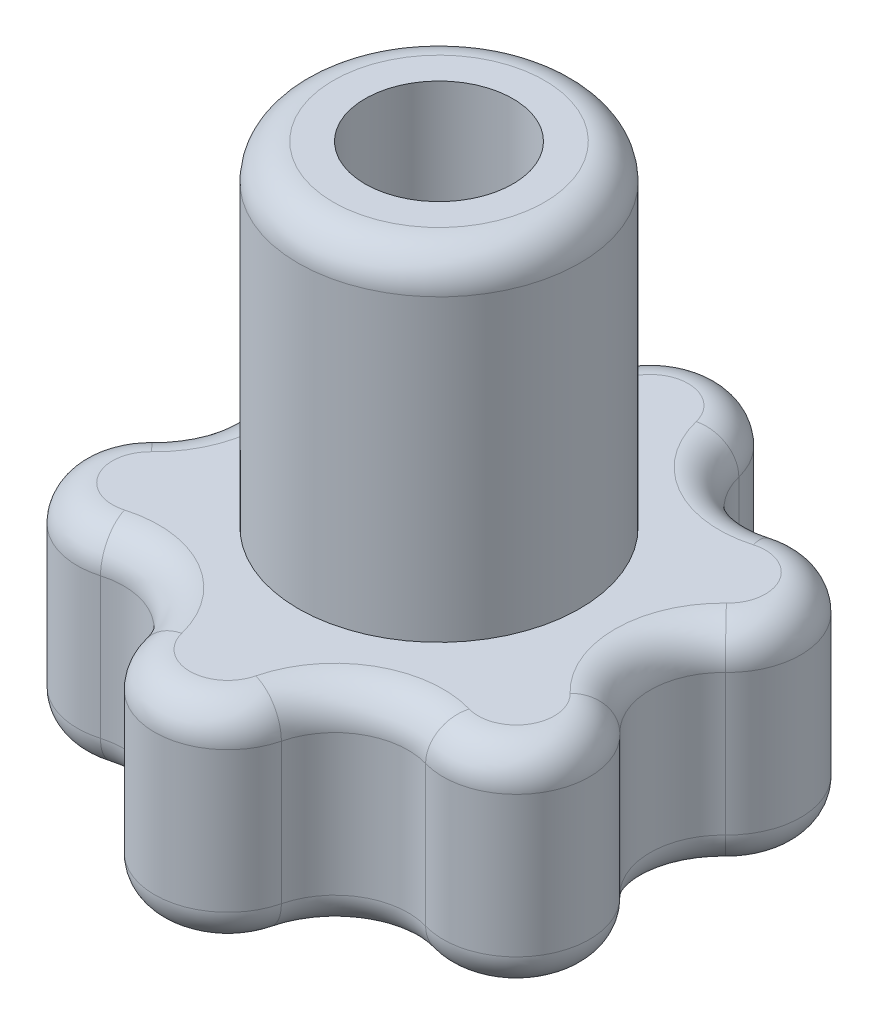
SolidWorks part; units mm, degrees
ref_plane "Спереди" through (0, 0, 0) normal (0, 0, 1) x (1, 0, 0)
ref_plane "Сверху" through (0, 0, 0) normal (0, 1, 0) x (1, 0, 0)
ref_plane "Справа" through (0, 0, 0) normal (1, 0, 0) x (0, 0, -1)
sketch "Эскиз1" plane through (0, 0, 0) normal (0, 1, 0) x (1, 0, 0)
  line L1 (0, 4.2147) -> (-3.65, 2.1073)
  line L2 (-3.65, 2.1073) -> (-3.65, -2.1073)
  line L3 (-3.65, -2.1073) -> (0, -4.2147)
  line L4 (0, -4.2147) -> (3.65, -2.1073)
  line L5 (3.65, -2.1073) -> (3.65, 2.1073)
  line L6 (3.65, 2.1073) -> (0, 4.2147)
  circle A0 centre (0, 0) radius 6 construction
  arc A1 (2.0203, 6.4992) -> (-2.0203, 6.4992) centre (0, 6) ccw
  arc A2 (2.0203, 6.4992) -> (4.6183, 4.9992) centre (4.0405, 6.9984) ccw
  arc A3 (-2.0203, -6.4992) -> (2.0203, -6.4992) centre (0, -6) ccw
  arc A4 (4.6183, -4.9992) -> (2.0203, -6.4992) centre (4.0405, -6.9984) ccw
  arc A5 (6.6386, 1.5) -> (4.6183, 4.9992) centre (5.1962, 3) ccw
  arc A6 (6.6386, 1.5) -> (6.6386, -1.5) centre (8.081, 0) ccw
  arc A7 (4.6183, -4.9992) -> (6.6386, -1.5) centre (5.1962, -3) ccw
  arc A8 (-4.6183, 4.9992) -> (-2.0203, 6.4992) centre (-4.0405, 6.9984) ccw
  arc A9 (-4.6183, 4.9992) -> (-6.6386, 1.5) centre (-5.1962, 3) ccw
  arc A10 (-6.6386, -1.5) -> (-6.6386, 1.5) centre (-8.081, 0) ccw
  arc A11 (-2.0203, -6.4992) -> (-4.6183, -4.9992) centre (-4.0405, -6.9984) ccw
  arc A12 (-6.6386, -1.5) -> (-4.6183, -4.9992) centre (-5.1962, -3) ccw
  circle A13 centre (0, 0) radius 3.65 construction
  dimension "D1" = 12
  dimension "D2" = 7.3
extrude "Бобышка-Вытянуть1" add sketch "Эскиз1" along normal blind 6 contours A7 A6 A5 A2 A1 A8 A9 A10 A12 A11 A3 A4
sketch "Эскиз2" plane through (0, 6, 0) normal (0, 1, 0) x (1, 0, 0)
  circle A0 centre (0, 0) radius 4
  dimension "D1" = 8
extrude "Бобышка-Вытянуть2" add sketch "Эскиз2" along normal blind 9.5
sketch "Эскиз3" plane through (0, 15.5, 0) normal (0, 1, 0) x (1, 0, 0)
  circle A0 centre (0, 0) radius 2.1
  dimension "D1" = 4.2
extrude "Вырез-Вытянуть1" cut sketch "Эскиз3" against normal through all
extrude "Вырез-Вытянуть2" cut sketch "Эскиз1<3>" along normal blind 3 contours L1 L2 L3 L4 L5 L6
sketch "Эскиз1<3>" plane through (0, 0, 0) normal (0, 1, 0) x (1, 0, 0) same geometry as "Эскиз1"
fillet "Скругление1" radius 1 25 edges at (-3, 6, 5.1962) (-6.9984, 6, 4.0405) (-6, 6, 0) (-6.9984, 6, -4.0405) (-3, 6, -5.1962) (0, 6, -8.081) (3, 6, -5.1962) (6.9984, 6, -4.0405) (6, 6, 0) (6.9984, 6, 4.0405) (3, 6, 5.1962) (-3, 0, 5.1962) (-6.9984, 0, 4.0405) (-6, 0, 0) (-6.9984, 0, -4.0405) (-3, 0, -5.1962) (0, 0, -8.081) (3, 0, -5.1962) (6.9984, 0, -4.0405) (6, 0, 0) (6.9984, 0, 4.0405) (3, 0, 5.1962) (0, 15.5, 4) (0, 6, 8.081) (0, 0, 8.081)
